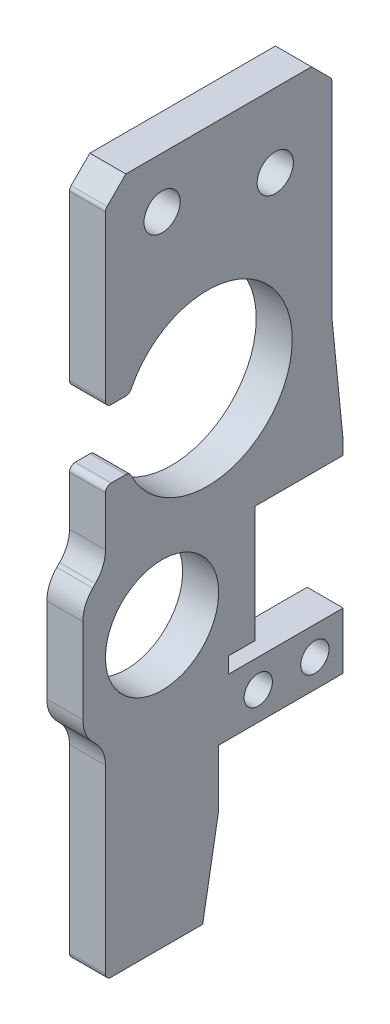
SolidWorks part; units mm, degrees
ref_plane "Front Plane" through (0, 0, 0) normal (0, 0, 1) x (1, 0, 0)
ref_plane "Top Plane" through (0, 0, 0) normal (0, 1, 0) x (1, 0, 0)
ref_plane "Right Plane" through (0, 0, 0) normal (1, 0, 0) x (0, 0, -1)
sketch "Sketch1" plane through (0, 0, 0) normal (1, 0, 0) x (0, 0, -1)
  line L0 (0, 0) -> (0, 17.7)
  line L1 (0, 17.7) -> (-2, 19.7)
  line L2 (-2, 19.7) -> (-2, 29.7)
  line L3 (-2, 29.7) -> (0, 31.7)
  line L4 (0, 31.7) -> (0, 60.81)
  line L5 (0, 60.81) -> (20, 60.81)
  line L7 (21, 29.68) -> (13.2, 29.68)
  line L8 (10.85, 19.4) -> (10.85, 18)
  line L9 (10.85, 18) -> (21, 18)
  line L10 (21, 18) -> (21, 13)
  line L11 (21, 13) -> (10, 13)
  line L12 (10, 13) -> (10, 0)
  line L13 (10, 0) -> (0, 0)
  line L14 (-8.9356, -4) -> (60.4069, -4) construction
  line L15 (5, 29.7) -> (-2, 29.7) construction
  line L16 (5, 19.7) -> (-2, 19.7) construction
  line L17 (0, 17.7) -> (0, 31.7) construction
  line L18 (10.85, 19.4) -> (13.2, 19.4)
  line L19 (13.2, 19.4) -> (13.2, 29.68)
  line L23 (20, 60.81) -> (20, 40.81)
  line L24 (20, 40.81) -> (21, 40.81)
  line L25 (21, 40.81) -> (21, 29.68)
  circle A0 centre (5, 24.7) radius 5
  circle A1 centre (5, 56.31) radius 1.6
  circle A2 centre (15, 54.31) radius 1.6
  circle A3 centre (18.5, 15.5) radius 1.25
  circle A4 centre (13.5, 15.5) radius 1.25
  point P12 (5, 0)
  dimension "D11" = 10
  dimension "D13" = 3.2
  dimension "D17" = 5
  dimension "D21" = 2.5
  dimension "D2" = 60.81
  dimension "D3" = 13
  dimension "D4" = 5
  dimension "D5" = 11.68
  dimension "D6" = 10.15
  dimension "D7" = 10
  dimension "D8" = 4
  dimension "D9" = 2
  dimension "D10" = 2
  dimension "D12" = 28.7
  dimension "D14" = 6.5
  dimension "D15" = 4.5
  dimension "D16" = 5
  dimension "D18" = 5
  dimension "D19" = 2.5
  dimension "D20" = 2.5
  dimension "D22" = 1.4
  dimension "D23" = 2.35
  dimension "D24" = 20
  dimension "D25" = 11
  dimension "D26" = 1
  dimension "D27" = 20
extrude "Boss-Extrude1" add sketch "Sketch1" along normal blind 3.18
chamfer "Chamfer1" distance 8 angle 10 1 edges at (1.59, 0, -10) first distance on face at (1.59, 6.5, -10)
fillet "Fillet1" [suppressed] radius 1
sketch "Sketch3" [suppressed] plane through (0, 0, 0) normal (1, 0, 0) x (0, 0, -1)
  line L1 (-15.4326, 41.7448) -> (-4.9749, 45.9147) construction
  line L2 (-4.9749, 45.9147) -> (-6.5925, 34.7732) construction
  line L3 (-6.5925, 34.7732) -> (-15.4326, 41.7448) construction
  line L4 (0, 60.81) -> (0, 32.9426) construction
  circle A0 centre (-9, 40.8109) radius 5
  circle A2 centre (-9, 40.8109) radius 6.5 construction
  circle A3 centre (-4.9749, 45.9147) radius 1.2 construction
  circle A4 centre (-6.5925, 34.7732) radius 1.2 construction
  circle A5 centre (-15.4326, 41.7448) radius 1.2 construction
  circle A6 centre (-5, 24.7) radius 5 construction
  dimension "D1" = 10
  dimension "D3" = 16.6
  dimension "D4" = 13
  dimension "D5" = 2.4
  dimension "D2" = 9
hole_wizard "CSK for M2 Flat Head Machine Screw1" [suppressed] positions "Sketch6" profile "Sketch7" countersink size "M2" standard "ANSI Metric"
sketch "Sketch6" plane through (0, 0, 0) normal (-1, 0, 0) x (0, 0, 1)
  point P0 (-4.9749, 45.9147)
  point P3 (-15.4326, 41.7448)
  point P6 (-6.5925, 34.7732)
sketch "Sketch7" plane through (0, 45.9147, -4.9749) normal (0, 1, 0) x (0, 0, 1)
  line L0 (0, 0) -> (0, 4.23)
  line L1 (0, 4.23) -> (1.2, 3.509)
  line L2 (1.2, 3.509) -> (1.2, 1)
  line L3 (1.2, 1) -> (2.2, 0)
  line L5 (2.2, 0) -> (0, 0)
  line L6 (-1.2, 1) -> (-2.2, 0) construction
  line L10 (0, 4.23) -> (-1.2, 3.509) construction
  line L11 (0, -6.35) -> (0, 107.95) construction
  dimension "Hole Dia." = 2.4
  dimension "Hole Depth" = 4.23
  dimension "Near C'Sink Dia." = 4.4
  dimension "Near C'Sink Angle" = 90
  dimension "Drill Angle" = 118
extrude "Cut-Extrude4" [suppressed] cut sketch "Sketch3" against normal through all
sketch "Sketch8" plane through (3.18, 0, 0) normal (1, 0, 0) x (0, 0, -1)
  line L0 (0, 60.81) -> (0, 31.7) construction
  line L1 (9, 40.8109) -> (0, 40.8109) construction
  line L2 (0, 43.8109) -> (2.1261, 43.8109)
  line L3 (2.1261, 37.8109) -> (0, 37.8109)
  line L4 (0, 37.8109) -> (0, 43.8109)
  arc A0 (2.1261, 37.8109) -> (2.1261, 43.8109) centre (9, 40.8109) ccw
  circle A1 centre (5, 24.7) radius 5 construction
  point P11 (0, 40.8109)
  dimension "D1" = 16.6
  dimension "D2" = 15
  dimension "D3" = 9
  dimension "D4" = 6
extrude "Cut-Extrude5" cut sketch "Sketch8" against normal through all
fillet "Fillet2" radius 3 4 edges at (1.59, 17.7, 0) (1.59, 19.7, 2) (1.59, 29.7, 2) (1.59, 31.7, 0)
fillet "Chamfer3" radius 10 1 edges at (1.59, 40.81, -21) profile chamfer first distance on face at (1.59, 35.245, -21)
fillet "Chamfer2" radius 1.8 2 edges at (1.59, 60.81, -20) (1.59, 60.81, 0) profile chamfer
fillet "Fillet4" radius 0.5 7 edges at (1.59, 59.01, 0) (1.59, 0, 0) (1.59, 37.8109, 0) (1.59, 37.8109, -2.1261) (1.59, 43.8109, -2.1261) (1.59, 43.8109, 0) (1.59, 59.01, -20)
